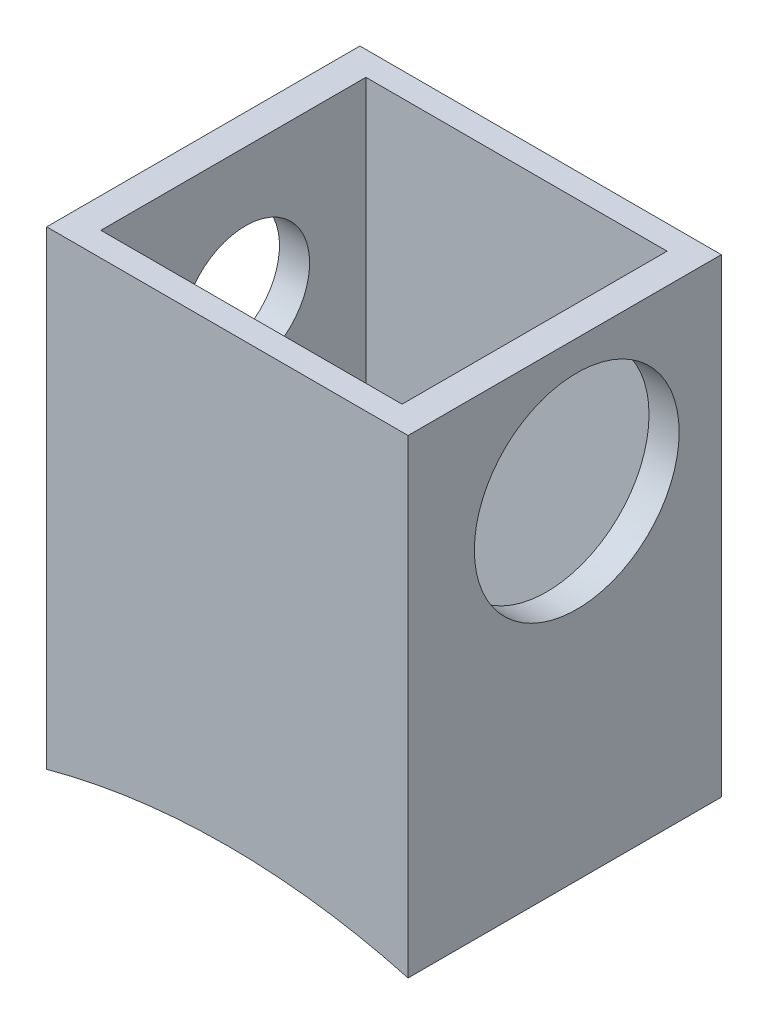
SolidWorks part; units mm, degrees
ref_plane "Front Plane" through (0, 0, 0) normal (0, 0, 1) x (1, 0, 0)
ref_plane "Top Plane" through (0, 0, 0) normal (0, 1, 0) x (1, 0, 0)
ref_plane "Right Plane" through (0, 0, 0) normal (1, 0, 0) x (0, 0, -1)
sketch "Sketch1" plane through (0, 0, 0) normal (0, 0, 1) x (1, 0, 0)
  line L0 (-3.3539, 7.6142) -> (-3.3539, -2.2918)
  line L1 (-3.3539, -2.2918) -> (4.2661, -2.2918)
  line L2 (4.2661, -2.2918) -> (4.2661, 7.6142)
  line L3 (3.6311, 7.6142) -> (3.6311, -0.7678)
  line L4 (3.6311, -0.7678) -> (-2.7189, -0.7678)
  line L5 (-2.7189, -0.7678) -> (-2.7189, 7.6142)
  line L6 (-2.7189, 7.6142) -> (-3.3539, 7.6142)
  line L7 (3.6311, 7.6142) -> (4.2661, 7.6142)
  dimension "D1" = 6.35
  dimension "D2" = 7.62
  dimension "D3" = 0.635
  dimension "D4" = 8.382
  dimension "D5" = 9.906
  dimension "D6" = 8.382
extrude "Boss-Extrude1" add sketch "Sketch1" along normal blind 5.588
sketch "Sketch2" plane through (-3.3539, 0, 0) normal (-1, 0, 0) x (0, 0, 1)
  line L0 (5.588, 7.6142) -> (0, 7.6142) construction
  line L1 (3.048, -2.2918) -> (3.048, 7.6142) construction
  point P0 (3.048, 4.8202)
  dimension "D1" = 2.794
hole_wizard "#6-32 Tapped Hole1" positions "Sketch3" profile "Sketch4" tap size "#6-32" standard "ANSI Inch" end condition up to next
sketch "Sketch3" plane through (-3.3539, 0, 0) normal (-1, 0, 0) x (0, 0, 1)
  point P0 (3.048, 4.8202)
sketch "Sketch4" plane through (-3.3539, 4.8202, 3.048) normal (0, 1, 0) x (0, 0, 1)
  line L0 (0, 0) -> (0, 0.635)
  line L1 (0, 0.635) -> (1.3525, 0.635)
  line L2 (1.3525, 0.635) -> (1.3525, 0)
  line L5 (1.3525, 0) -> (0, 0)
  line L11 (0, -6.35) -> (0, 107.95) construction
  dimension "Thread Major Dia." = 2.7051
  dimension "Thru Tap Drill Depth" = 0.635
sketch "Sketch5" plane through (4.2661, 0, 0) normal (1, 0, 0) x (0, 0, -1)
  point P0 (-3.048, 4.8202)
sketch "Sketch6" plane through (4.2661, 0, 0) normal (1, 0, 0) x (0, 0, -1)
  circle A0 centre (-3.048, 4.8202) radius 2.159
extrude "Cut-Extrude1" cut sketch "Sketch6" against normal up to next
sketch "Sketch12" plane through (-3.3539, 0, 0) normal (-1, 0, 0) x (0, 0, 1)
  line L0 (2.794, -2.2918) -> (2.794, 7.6142) construction
  line L1 (5.588, -2.2918) -> (0, -2.2918) construction
  line L2 (5.588, 7.6142) -> (0, 7.6142) construction
ref_plane "Plane1" through (0.508, 0, 0) normal (1, 0, 0) x (0, 0, -1)
sketch "Sketch16" plane through (0, 0, 0) normal (0, 0, -1) x (-1, 0, 0)
  line L0 (-4.2661, -2.2918) -> (-0.4561, -16.2595) construction
  line L1 (-0.4561, -16.2595) -> (3.3539, -2.2918) construction
  line L2 (3.3539, -2.2918) -> (-4.2661, -2.2918)
  arc A0 (-4.2661, -2.2918) -> (3.3539, -2.2918) centre (-0.4561, -16.2595) cw
  dimension "D1" = 14.478
  dimension "D2" = 14.478
extrude "Cut-Extrude2" cut sketch "Sketch16" against normal through all
sketch "Sketch19" plane through (0, 0, 5.588) normal (0, 0, 1) x (1, 0, 0)
  line L0 (4.2661, -2.2918) -> (4.2661, 7.6142) construction
  line L1 (4.2661, 7.6142) -> (3.6311, 7.6142)
  line L5 (-2.7189, 7.6142) -> (-3.3539, 7.6142)
  line L6 (-3.3539, 7.6142) -> (-3.3539, -2.2918)
  line L7 (4.2661, -2.2918) -> (4.2661, 7.6142)
  line L8 (3.6311, 7.6142) -> (-2.7189, 7.6142)
  arc A0 (-3.3539, -2.2918) -> (4.2661, -2.2918) centre (0.4561, -16.2595) cw
extrude "Boss-Extrude3" add sketch "Sketch19" along normal blind 1.016
sketch "Sketch20" plane through (0, 7.6142, 0) normal (0, 1, 0) x (1, 0, 0)
  line L0 (-2.7189, -5.588) -> (-2.7189, -8.1549)
  line L1 (-2.7189, -5.588) -> (3.6311, -5.588)
  line L2 (3.6311, -5.588) -> (3.6311, -8.1549)
  line L3 (3.6311, -8.1549) -> (-2.7189, -8.1549)
extrude "Cut-Extrude3" cut sketch "Sketch20" against normal blind 8.382
sketch "Sketch22" plane through (0, 0, 6.604) normal (0, 0, 1) x (1, 0, 0)
  line L0 (-2.7189, 7.6142) -> (-2.7189, -0.7678)
  line L1 (-2.7189, -0.7678) -> (3.6311, -0.7678)
  line L2 (3.6311, -0.7678) -> (3.6311, 7.6142)
  line L3 (3.6311, 7.6142) -> (-2.7189, 7.6142)
extrude "Boss-Extrude4" add sketch "Sketch22" against normal blind 0.508
sketch "Sketch24" plane through (0, 0, 0) normal (0, 0, -1) x (-1, 0, 0)
  line L0 (2.7189, -0.7678) -> (2.7189, 7.6142)
  line L1 (2.7189, 7.6142) -> (-3.6311, 7.6142)
  line L2 (-3.6311, 7.6142) -> (-3.6311, -0.7678)
  line L3 (-3.6311, -0.7678) -> (2.7189, -0.7678)
extrude "Boss-Extrude5" add sketch "Sketch24" against normal blind 0.508
ref_plane "Plane2" through (0, 0, 3.302) normal (0, 0, -1) x (-1, 0, 0)
